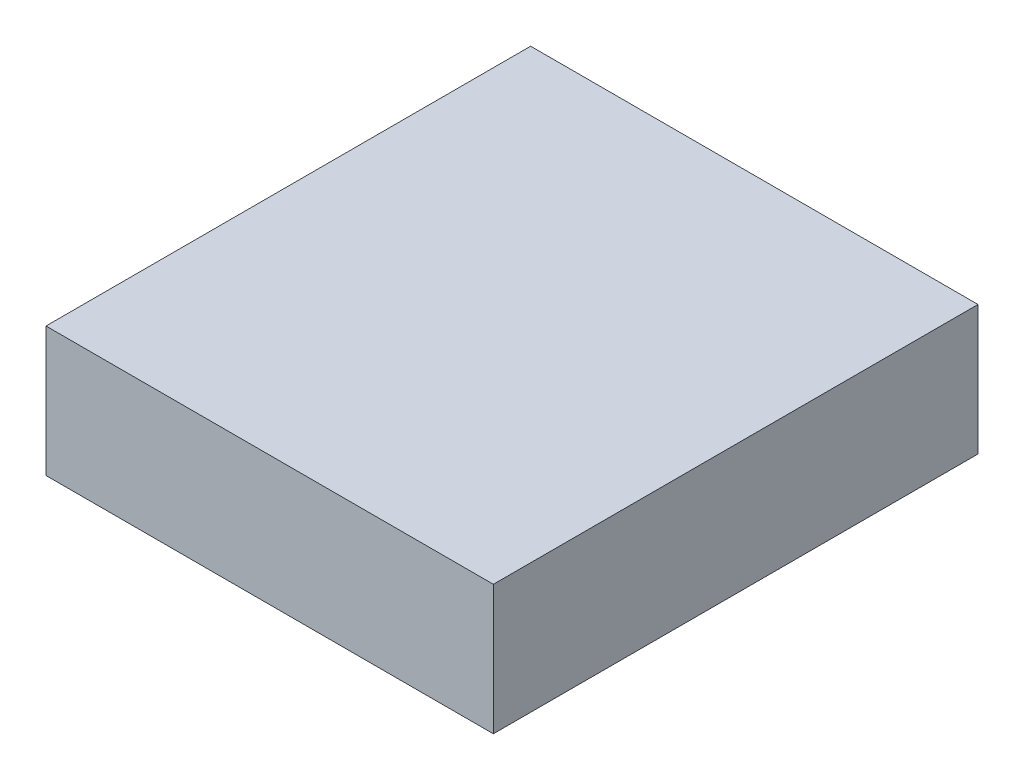
SolidWorks part; units mm, degrees
ref_plane "Front Plane" through (0, 0, 0) normal (0, 0, 1) x (1, 0, 0)
ref_plane "Top Plane" through (0, 0, 0) normal (0, 1, 0) x (1, 0, 0)
ref_plane "Right Plane" through (0, 0, 0) normal (1, 0, 0) x (0, 0, -1)
sketch "Sketch1" plane through (0, 0, 0) normal (0, 1, 0) x (1, 0, 0)
  line L1 (0, 0) -> (34.5428, 0)
  line L2 (0, 0) -> (0, 37.4214)
  line L3 (0, 37.4214) -> (34.5428, 37.4214)
  line L4 (34.5428, 0) -> (34.5428, 37.4214)
extrude "Boss-Extrude1" add sketch "Sketch1" along normal blind 10
